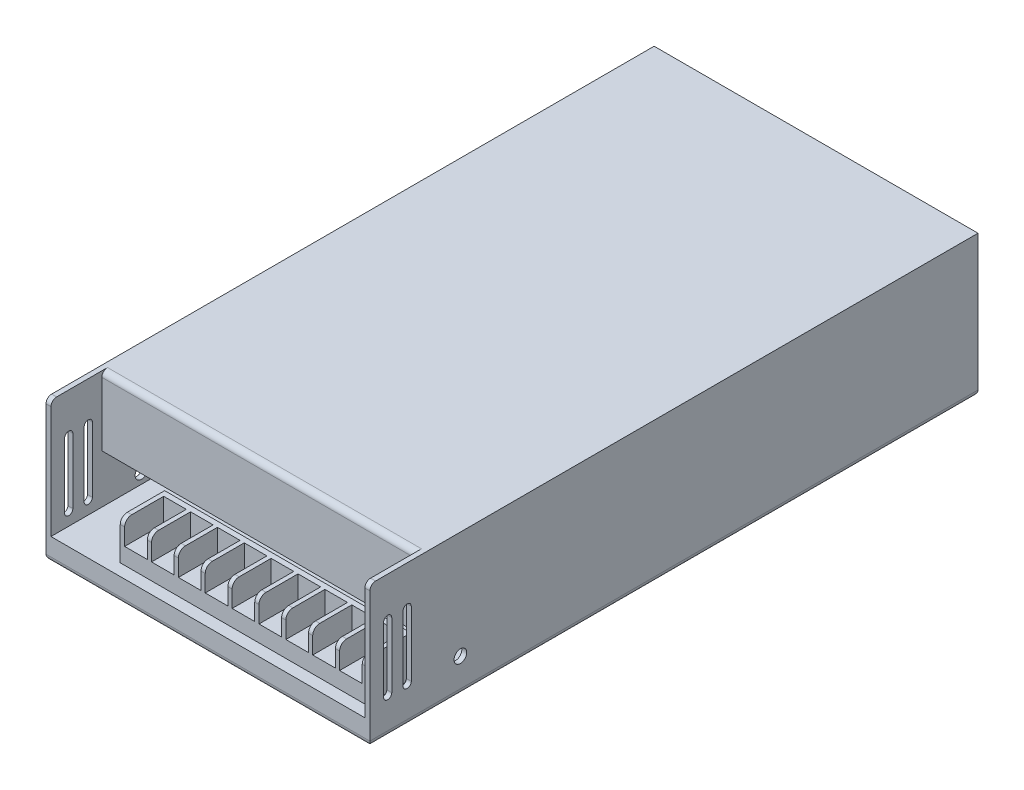
SolidWorks part; units mm, degrees
material "2024 Alloy"
ref_plane "Front Plane" through (0, 0, 0) normal (0, 0, 1) x (1, 0, 0)
ref_plane "Top Plane" through (0, 0, 0) normal (0, 1, 0) x (1, 0, 0)
ref_plane "Right Plane" through (0, 0, 0) normal (1, 0, 0) x (0, 0, -1)
sketch "Sketch1" plane through (0, 0, 0) normal (0, 1, 0) x (1, 0, 0)
  line L0 (0, 197) -> (0, -18) construction
  line L1 (-57.25, -18) -> (57.25, -18)
  line L2 (-57.25, -18) -> (-57.25, 197)
  line L3 (-57.25, 197) -> (57.25, 197)
  line L4 (57.25, -18) -> (57.25, 197)
  line L5 (-57.25, 0) -> (57.25, 0) construction
  dimension "D1" = 215
  dimension "D2" = 18
  dimension "D3" = 114.5
extrude "Boss-Extrude1" add sketch "Sketch1" along normal blind 41.75 and the other way blind 8.25
sketch "Sketch2" plane through (0, 0, 18) normal (0, 0, 1) x (1, 0, 0)
  line L0 (-57.25, 41.75) -> (57.25, 41.75) construction
  line L1 (-55.5, 0) -> (55.5, 0)
  line L2 (-55.5, 0) -> (-55.5, 41.75)
  line L3 (-55.5, 41.75) -> (55.5, 41.75)
  line L4 (55.5, 0) -> (55.5, 41.75)
  line L5 (0, 0) -> (0, 41.75) construction
  line L6 (57.25, -8.25) -> (57.25, 41.75) construction
  dimension "D1" = 1.75
extrude "Cut-Extrude1" cut sketch "Sketch2" against normal blind 18
sketch "Sketch3" plane through (57.25, 0, 0) normal (1, 0, 0) x (0, 0, -1)
  line L0 (-11.71, 27.7) -> (-11.71, 4.7) construction
  line L1 (-10.26, 27.7) -> (-10.26, 4.7)
  line L2 (-13.16, 27.7) -> (-13.16, 4.7)
  line L3 (-4.81, 27.7) -> (-4.81, 4.7) construction
  line L4 (-3.36, 27.7) -> (-3.36, 4.7)
  line L5 (-6.26, 27.7) -> (-6.26, 4.7)
  line L6 (-11.71, 16.2) -> (-4.81, 16.2) construction
  line L7 (-18, -8.25) -> (-18, 41.75) construction
  line L8 (-11.71, 29.15) -> (-11.71, 41.75) construction
  line L9 (-18, 41.75) -> (197, 41.75) construction
  line L10 (-11.71, 3.25) -> (-11.71, -8.25) construction
  line L11 (-18, -8.25) -> (197, -8.25) construction
  arc A0 (-10.26, 27.7) -> (-13.16, 27.7) centre (-11.71, 27.7) ccw
  arc A1 (-13.16, 4.7) -> (-10.26, 4.7) centre (-11.71, 4.7) ccw
  arc A2 (-3.36, 27.7) -> (-6.26, 27.7) centre (-4.81, 27.7) ccw
  arc A3 (-6.26, 4.7) -> (-3.36, 4.7) centre (-4.81, 4.7) ccw
  point P2 (-11.71, 16.2)
  point P7 (-4.81, 16.2)
  dimension "D1" = 4.84
  dimension "D2" = 2.9
  dimension "D3" = 4
  dimension "D4" = 12.6
  dimension "D5" = 11.5
extrude "Cut-Extrude2" cut sketch "Sketch3" against normal through all
fillet "Fillet1" radius 2 7 edges at (0, -8.25, -197) (-57.25, -8.25, -89.5) (0, -8.25, 18) (57.25, -8.25, -89.5) (0, 41.75, 0) (56.375, 41.75, 18) (-56.375, 41.75, 18)
sketch "Sketch4" plane through (0, 0, 0) normal (0, 1, 0) x (-1, 0, 0)
  line L0 (55.5, 0) -> (-55.5, 0) construction
  line L1 (35.2, 0) -> (-51.85, 0)
  line L2 (35.2, 0) -> (35.2, 13.8)
  line L3 (35.2, 13.8) -> (-51.85, 13.8)
  line L4 (-51.85, 0) -> (-51.85, 13.8)
  line L5 (55.5, 18) -> (-55.5, 18) construction
  line L6 (-55.5, 0) -> (-55.5, 18) construction
  line L7 (55.5, 0) -> (55.5, 18) construction
  dimension "D1" = 4.2
  dimension "D2" = 3.65
  dimension "D3" = 20.3
extrude "Boss-Extrude2" add sketch "Sketch4" along normal blind 14.25 separate body
sketch "Sketch7" plane through (0, 0, 0) normal (0, 0, 1) x (1, 0, 0)
  line L0 (-55.5, 39.75) -> (-55.5, 0) construction
  line L1 (-55.5, 17.25) -> (55.5, 17.25)
  line L2 (-55.5, 17.25) -> (-55.5, 0)
  line L3 (-55.5, 0) -> (55.5, 0)
  line L4 (55.5, 17.25) -> (55.5, 0)
  line L5 (-55.5, 0) -> (55.5, 0) construction
  line L6 (51.85, 14.25) -> (-35.2, 14.25) construction
  line L7 (55.5, 0) -> (55.5, 39.75) construction
  dimension "D1" = 3
extrude "Cut-Extrude4" cut sketch "Sketch7" against normal offset from surface (195.25 mm away) 1.75 up to face at (0, 17.75, -197)
fillet "Fillet2" radius 2.5 1 edges at (8.325, 14.25, 13.8)
sketch "Sketch6" plane through (0, 0, 13.8) normal (0, 0, 1) x (1, 0, 0)
  line L0 (-35.2, 14.25) -> (51.85, 14.25) construction
  line L1 (42.35, 14.25) -> (50.35, 14.25)
  line L2 (42.35, 14.25) -> (42.35, 5.8)
  line L3 (42.35, 5.8) -> (50.35, 5.8)
  line L4 (50.35, 14.25) -> (50.35, 5.8)
  line L6 (51.85, 11.75) -> (51.85, 0) construction
  line L7 (-35.2, 0) -> (51.85, 0) construction
  dimension "D1" = 5.8
  dimension "D2" = 1.5
  dimension "D3" = 8
extrude "Cut-Extrude3" cut sketch "Sketch6" against normal up to surface (13.8 mm away) up to face at (0, 28.5, 0)
sketch "Sketch9" plane through (0, 0, 0) normal (0, 0, -1) x (-1, 0, 0)
  line L0 (35.2, 14.25) -> (35.2, 0) construction
  line L1 (-51.85, 14.25) -> (35.2, 14.25)
  line L2 (-51.85, 14.25) -> (-51.85, 0.5)
  line L3 (-51.85, 0.5) -> (35.2, 0.5)
  line L4 (35.2, 14.25) -> (35.2, 0.5)
  line L5 (-51.85, 0) -> (35.2, 0) construction
  dimension "D1" = 0.5
extrude "Boss-Extrude6" add sketch "Sketch9" along normal blind 1.9
pattern_linear "LPattern1" count 9 spacing 9.5 along (1, 0, 0) of "Cut-Extrude3"
hole_wizard "M3 Clearance Hole2" positions "Sketch14" profile "Sketch13" hole size "M3" standard "Ansi Metric"
sketch "Sketch14" plane through (0, -8.25, 0) normal (0, -1, 0) x (1, 0, 0)
  line L0 (-57.25, 18) -> (57.25, 18) construction
  line L2 (-57.25, -197) -> (-57.25, 18) construction
  line L3 (57.25, -197) -> (-57.25, -197) construction
  line L4 (57.25, 18) -> (57.25, -197) construction
  point P0 (-47.5, -8.75)
  point P1 (47.5, -8.75)
  point P3 (47.5, -186.5)
  point P5 (-47.5, -186.5)
  dimension "D1" = 26.75
  dimension "D2" = 9.75
  dimension "D3" = 10.5
  dimension "D4" = 9.75
sketch "Sketch13" plane through (-47.5, -8.25, -8.75) normal (1, 0, 0) x (0, 0, -1)
  line L0 (0, 0) -> (0, 3.0215)
  line L1 (0, 3.0215) -> (1.7, 2)
  line L2 (1.7, 2) -> (1.7, 0)
  line L5 (1.7, 0) -> (0, 0)
  line L10 (0, 3.0215) -> (-1.7, 2) construction
  line L11 (0, -6.35) -> (0, 107.95) construction
  dimension "Hole Dia." = 3.4
  dimension "Hole Depth" = 2
  dimension "Drill Angle" = 118
hole_wizard "M4 Clearance Hole1" positions "Sketch16" profile "Sketch15" hole size "M4" standard "Ansi Metric"
sketch "Sketch16" plane through (57.25, 0, 0) normal (1, 0, 0) x (0, 0, -1)
  line L0 (-18, -6.25) -> (-18, 39.75) construction
  line L1 (195, -8.25) -> (-16, -8.25) construction
  point P0 (14, 3.75)
  dimension "D1" = 32
  dimension "D2" = 12
sketch "Sketch15" plane through (57.25, 3.75, -14) normal (0, 1, 0) x (0, 0, -1)
  line L0 (0, 0) -> (0, 3.3519)
  line L1 (0, 3.3519) -> (2.25, 2)
  line L2 (2.25, 2) -> (2.25, 0)
  line L5 (2.25, 0) -> (0, 0)
  line L10 (0, 3.3519) -> (-2.25, 2) construction
  line L11 (0, -6.35) -> (0, 107.95) construction
  dimension "Hole Dia." = 4.5
  dimension "Hole Depth" = 2
  dimension "Drill Angle" = 118
mirror "M4 Hole Other Side" about plane through (0, 0, 0) normal (1, 0, 0) of "M4 Clearance Hole1"
